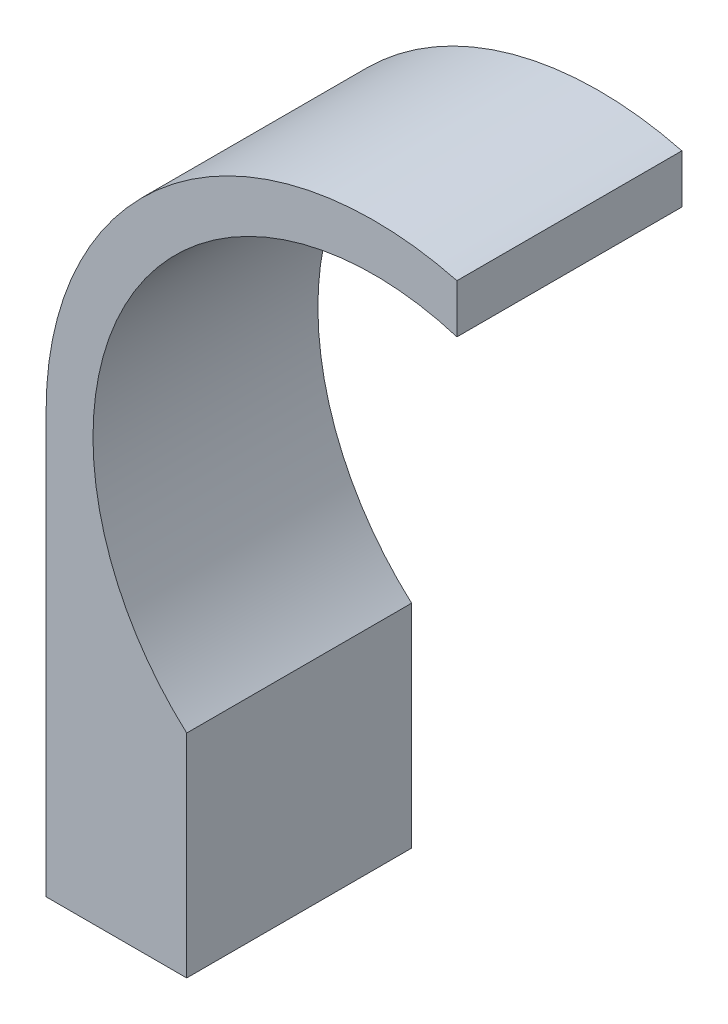
SolidWorks part; units mm, degrees
material "201 Annealed Stainless Steel (SS)"
ref_plane "Front Plane" through (0, 0, 0) normal (0, 0, 1) x (1, 0, 0)
ref_plane "Top Plane" through (0, 0, 0) normal (0, 1, 0) x (1, 0, 0)
ref_plane "Right Plane" through (0, 0, 0) normal (1, 0, 0) x (0, 0, -1)
sketch "Sketch1" plane through (0, 0, 0) normal (0, 0, 1) x (1, 0, 0)
  line L0 (0, 0) -> (0, -175) construction
  line L1 (-100, -111.8034) -> (-100, -225)
  line L2 (0, 0) -> (101.5936, 0) construction
  line L3 (44.2, 111.7322) -> (44.2, -25.0367) construction
  line L5 (44.2, 169.3262) -> (44.2, 143.34)
  line L7 (0, 0) -> (-138.7196, 0) construction
  line L8 (-175, 0) -> (-175, -225)
  line L9 (-100, -225) -> (-175, -225)
  line L10 (0, -175) -> (0, -225) construction
  line L11 (0, -225) -> (-200, -225) construction
  line L12 (-100, -111.8034) -> (100, -111.8034) construction
  line L13 (0, -150) -> (-100, -150) construction
  circle A0 centre (0, 0) radius 150 construction
  circle A1 centre (0, 0) radius 175 construction
  arc A2 (-100, -111.8034) -> (44.2, 143.34) centre (0, 0) cw
  arc A3 (-175, 0) -> (44.2, 169.3262) centre (0, 0) cw
  dimension "D1" = 300
  dimension "D2" = 350
  dimension "D6" = 175
  dimension "D5" = 50
  dimension "D4" = 44.2
  dimension "D7" = 200
extrude "Inner Ring - Left Side" add sketch "Sketch1" along normal blind 120
sketch "Sketch2" plane through (-100, 0, 0) normal (1, 0, 0) x (0, 0, -1)
  line L0 (0, -150) -> (-120, -150) construction
  line L1 (-120, -225) -> (-120, -111.8034) construction
